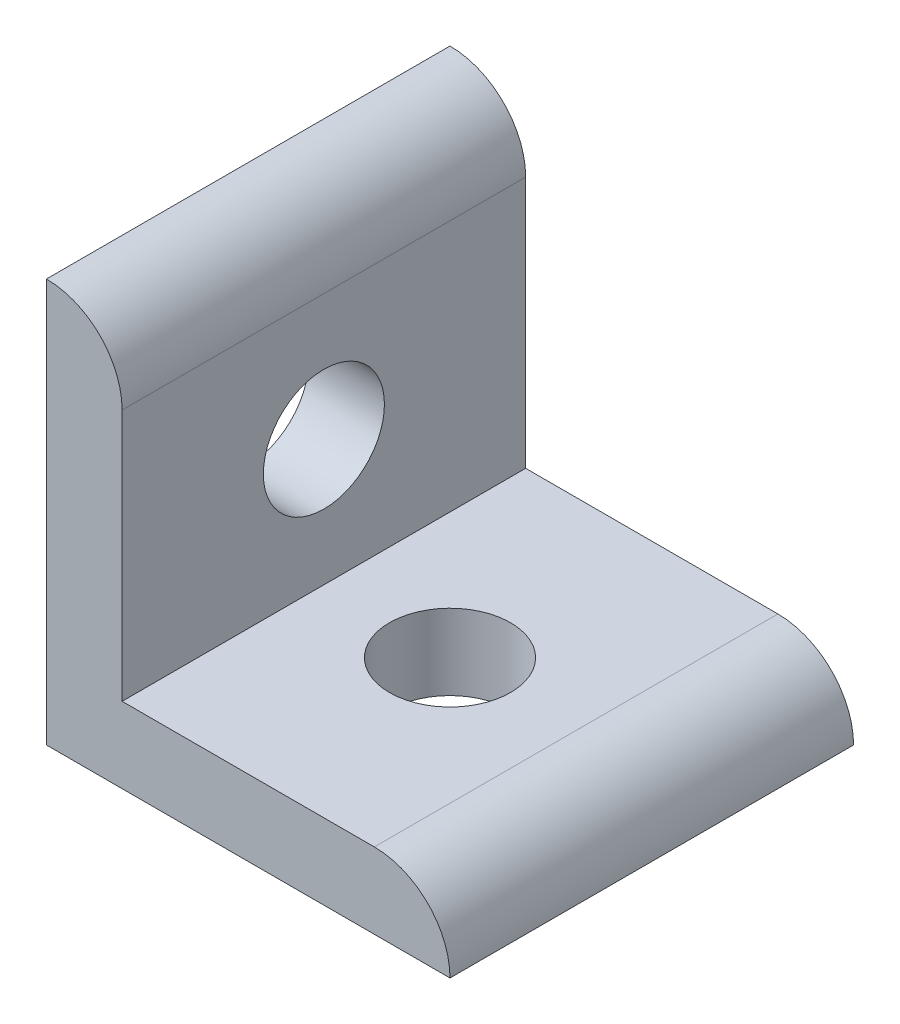
SolidWorks part; units mm, degrees
ref_plane "Front Plane" through (0, 0, 0) normal (0, 0, 1) x (1, 0, 0)
ref_plane "Top Plane" through (0, 0, 0) normal (0, 1, 0) x (1, 0, 0)
ref_plane "Right Plane" through (0, 0, 0) normal (1, 0, 0) x (0, 0, -1)
sketch "Sketch2" plane through (0, 0, 0) normal (0, 0, 1) x (1, 0, 0)
  line L1 (0, 0) -> (25.4, 0)
  line L2 (0, 0) -> (0, 25.4)
  line L3 (0, 25.4) -> (25.4, 25.4)
  line L4 (25.4, 0) -> (25.4, 25.4)
  dimension "D1" = 25.4
  dimension "D2" = 25.4
extrude "Boss-Extrude1" add sketch "Sketch2" along normal blind 25.4
shell "Shell1" thickness 4.7625 removed face at (25.4, 12.7, 12.7) removed face at (12.7, 25.4, 12.7) removed face at (12.7, 12.7, 25.4) removed face at (12.7, 12.7, 0)
fillet "Fillet1" radius 4.7625 2 edges at (25.4, 4.7625, 12.7) (4.7625, 25.4, 12.7)
sketch "Sketch3" plane through (0, 0, 0) normal (-1, 0, 0) x (0, 0, 1)
  line L0 (12.7, 0) -> (12.7, 25.4) construction
  line L1 (25.4, 0) -> (0, 0) construction
  line L2 (25.4, 25.4) -> (0, 25.4) construction
  circle A0 centre (12.7, 12.7) radius 3.81
  dimension "D1" = 7.62
extrude "Cut-Extrude1" cut sketch "Sketch3" against normal blind 25.4
ref_plane "Plane4" through (0, 0, 0) normal (-0.7071, 0.7071, 0) x (0.7071, 0.7071, 0)
mirror "Mirror1" about plane through (0, 0, 0) normal (-0.7071, 0.7071, 0) of "Cut-Extrude1"
